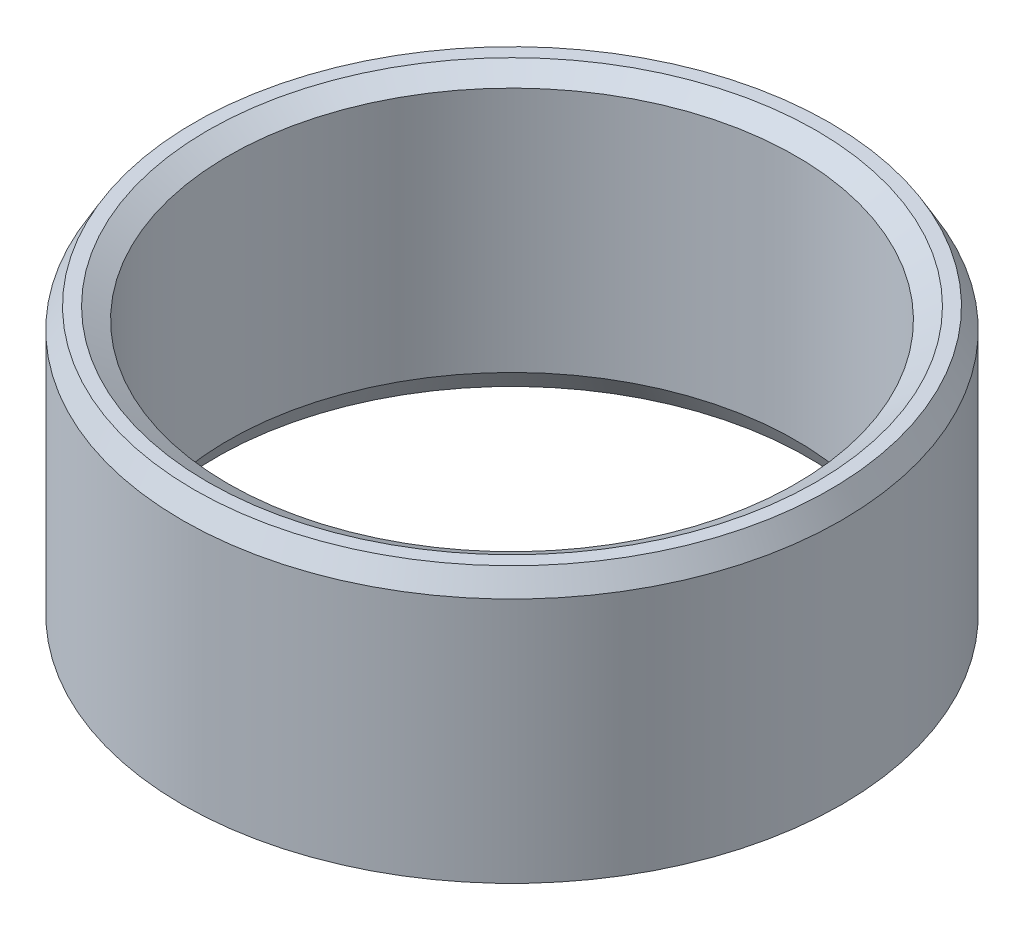
SolidWorks part; units mm, degrees
ref_plane "Front Plane" through (0, 0, 0) normal (0, 0, 1) x (1, 0, 0)
ref_plane "Top Plane" through (0, 0, 0) normal (0, 1, 0) x (1, 0, 0)
ref_plane "Right Plane" through (0, 0, 0) normal (1, 0, 0) x (0, 0, -1)
sketch "Sketch1" plane through (0, 0, 0) normal (0, 1, 0) x (1, 0, 0)
  circle A0 centre (0, 0) radius 55
  dimension "SLEEVE_OD" = 110
extrude "Boss-Extrude1" add sketch "Sketch1" along normal blind 46.4747
sketch "Sketch2" plane through (0, 0, 0) normal (0, 1, 0) x (1, 0, 0)
  circle A0 centre (0, 0) radius 47.3572
  dimension "BORE_D" = 94.7144
extrude "Cut-Extrude1" cut sketch "Sketch2" along normal through all
chamfer "Chamfer1" distance 3.4202 angle 30 4 edges at (0, 46.4747, 47.3572) (0, 0, 47.3572) (0, 0, 55) (0, 46.4747, 55) first distance on face at (0, 46.4747, 47.3572) first distance on face at (0, 0, 47.3572) first distance on face at (0, 46.4747, 55)
